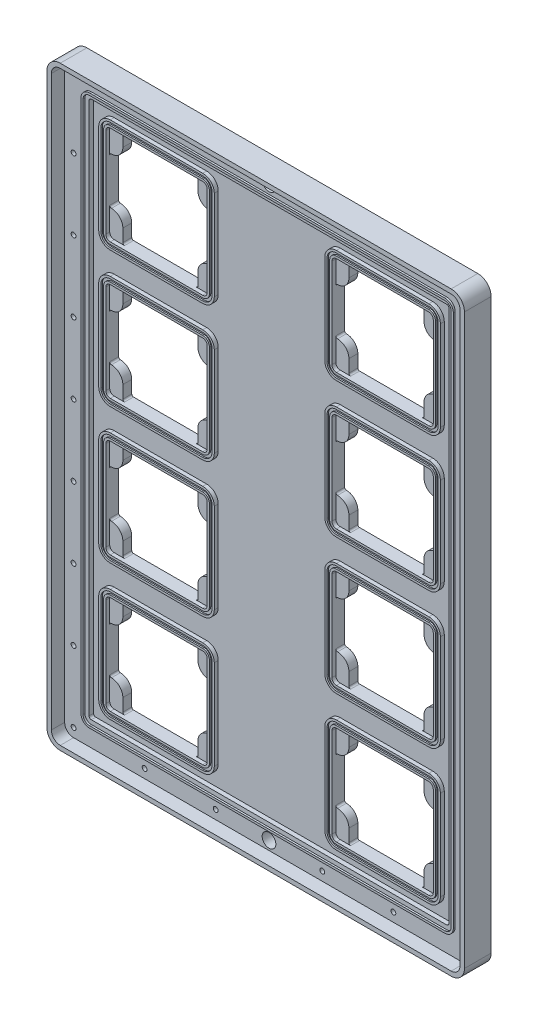
SolidWorks part; units mm, degrees
ref_plane "Front Plane" through (0, 0, 0) normal (0, 0, 1) x (1, 0, 0)
ref_plane "Top Plane" through (0, 0, 0) normal (0, 1, 0) x (1, 0, 0)
ref_plane "Right Plane" through (0, 0, 0) normal (1, 0, 0) x (0, 0, -1)
sketch "Sketch1" plane through (0, 0, 0) normal (0, 0, 1) x (1, 0, 0)
  line L1 (0, 0) -> (292.1, 0)
  line L2 (0, 0) -> (0, 419.1)
  line L3 (0, 419.1) -> (292.1, 419.1)
  line L4 (292.1, 0) -> (292.1, 419.1)
  dimension "D1" = 419.1
  dimension "D2" = 292.1
extrude "Boss-Extrude1" add sketch "Sketch1" along normal blind 9.525
sketch "Sketch4" plane through (0, 0, 9.525) normal (0, 0, 1) x (1, 0, 0)
  line L3 (0, 419.1) -> (0, 0) construction
  line L4 (6.35, 412.75) -> (285.75, 412.75) construction
  line L5 (6.35, 412.75) -> (6.35, 6.35) construction
  line L6 (6.35, 6.35) -> (285.75, 6.35) construction
  line L7 (285.75, 412.75) -> (285.75, 6.35) construction
  line L8 (292.1, 419.1) -> (0, 419.1) construction
  line L9 (292.1, 0) -> (292.1, 419.1) construction
  line L10 (0, 0) -> (292.1, 0) construction
  circle A0 centre (6.35, 6.35) radius 1.7272
  circle A1 centre (6.35, 412.75) radius 1.7272
  circle A2 centre (285.75, 412.75) radius 1.7272
  circle A3 centre (285.75, 6.35) radius 1.7272
  dimension "D5" = 3.4544
  dimension "D1" = 6.35
  dimension "D2" = 6.35
  dimension "D3" = 6.35
  dimension "D4" = 6.35
extrude "Cut-Extrude1" cut sketch "Sketch4" against normal blind 6.985
pattern_linear "LPattern2" count 8 spacing 50.8 along (0, -1, 0) of "Cut-Extrude1"
sketch "Sketch5" plane through (0, 0, 9.525) normal (0, 0, 1) x (1, 0, 0)
  line L0 (0, 419.1) -> (0, 0) construction
  line L1 (19.05, 406.4) -> (273.05, 406.4) construction
  line L2 (12.7, 400.05) -> (12.7, 19.05) construction
  line L3 (19.05, 12.7) -> (273.05, 12.7) construction
  line L4 (279.4, 400.05) -> (279.4, 19.05) construction
  line L5 (292.1, 419.1) -> (0, 419.1) construction
  line L6 (292.1, 0) -> (292.1, 419.1) construction
  line L7 (0, 0) -> (292.1, 0) construction
  line L8 (19.05, 14.732) -> (273.05, 14.732) construction
  line L9 (14.732, 400.05) -> (14.732, 19.05) construction
  line L10 (19.05, 404.368) -> (273.05, 404.368) construction
  line L11 (277.368, 400.05) -> (277.368, 19.05) construction
  line L12 (12.954, 400.05) -> (12.954, 19.05)
  line L13 (19.05, 406.146) -> (273.05, 406.146)
  line L14 (279.146, 400.05) -> (279.146, 19.05)
  line L15 (19.05, 12.954) -> (273.05, 12.954)
  line L16 (277.622, 400.05) -> (277.622, 19.05)
  line L17 (19.05, 404.622) -> (273.05, 404.622)
  line L18 (14.478, 400.05) -> (14.478, 19.05)
  line L19 (19.05, 14.478) -> (273.05, 14.478)
  arc A0 (273.05, 12.7) -> (279.4, 19.05) centre (273.05, 19.05) ccw construction
  arc A1 (12.7, 19.05) -> (19.05, 12.7) centre (19.05, 19.05) ccw construction
  arc A2 (273.05, 406.4) -> (279.4, 400.05) centre (273.05, 400.05) cw construction
  arc A3 (19.05, 406.4) -> (12.7, 400.05) centre (19.05, 400.05) ccw construction
  arc A4 (14.732, 19.05) -> (19.05, 14.732) centre (19.05, 19.05) ccw construction
  arc A5 (19.05, 404.368) -> (14.732, 400.05) centre (19.05, 400.05) ccw construction
  arc A6 (273.05, 404.368) -> (277.368, 400.05) centre (273.05, 400.05) cw construction
  arc A7 (273.05, 14.732) -> (277.368, 19.05) centre (273.05, 19.05) ccw construction
  arc A8 (19.05, 406.146) -> (12.954, 400.05) centre (19.05, 400.05) ccw
  arc A9 (273.05, 406.146) -> (279.146, 400.05) centre (273.05, 400.05) cw
  arc A10 (273.05, 12.954) -> (279.146, 19.05) centre (273.05, 19.05) ccw
  arc A11 (12.954, 19.05) -> (19.05, 12.954) centre (19.05, 19.05) ccw
  arc A12 (273.05, 404.622) -> (277.622, 400.05) centre (273.05, 400.05) cw
  arc A13 (19.05, 404.622) -> (14.478, 400.05) centre (19.05, 400.05) ccw
  arc A14 (14.478, 19.05) -> (19.05, 14.478) centre (19.05, 19.05) ccw
  arc A15 (273.05, 14.478) -> (277.622, 19.05) centre (273.05, 19.05) ccw
  dimension "D5" = 6.35
  dimension "D1" = 12.7
  dimension "D2" = 12.7
  dimension "D3" = 12.7
  dimension "D4" = 12.7
  dimension "D6" = 2.032
  dimension "D7" = 2.032
  dimension "D8" = 0.254
  dimension "D9" = 0.254
  dimension "D10" = 0.254
sketch "Sketch6" plane through (0, 0, 9.525) normal (0, 0, 1) x (1, 0, 0)
  line L0 (292.1, 419.1) -> (0, 419.1) construction
  line L1 (0, 419.1) -> (0, 0) construction
  line L24 (273.05, 401.6375) -> (19.05, 401.6375)
  line L25 (274.6375, 19.05) -> (274.6375, 400.05)
  line L26 (19.05, 17.4625) -> (273.05, 17.4625)
  line L27 (17.4625, 400.05) -> (17.4625, 19.05)
  line L28 (273.05, 401.6375) -> (19.05, 401.6375)
  line L29 (274.6375, 19.05) -> (274.6375, 400.05)
  line L30 (19.05, 17.4625) -> (273.05, 17.4625)
  line L31 (17.4625, 400.05) -> (17.4625, 19.05)
  arc A20 (19.05, 401.6375) -> (17.4625, 400.05) centre (19.05, 400.05) ccw
  arc A21 (274.6375, 400.05) -> (273.05, 401.6375) centre (273.05, 400.05) ccw
  arc A22 (273.05, 17.4625) -> (274.6375, 19.05) centre (273.05, 19.05) ccw
  arc A23 (17.4625, 19.05) -> (19.05, 17.4625) centre (19.05, 19.05) ccw
  arc A24 (19.05, 401.6375) -> (17.4625, 400.05) centre (19.05, 400.05) ccw
  arc A25 (274.6375, 400.05) -> (273.05, 401.6375) centre (273.05, 400.05) ccw
  arc A26 (273.05, 17.4625) -> (274.6375, 19.05) centre (273.05, 19.05) ccw
  arc A27 (17.4625, 19.05) -> (19.05, 17.4625) centre (19.05, 19.05) ccw
  dimension "D2" = 17.4625
  dimension "D3" = 17.4625
  dimension "D1" = 2.7305
extrude "Cut-Extrude3" cut sketch "Sketch6" against normal blind 3.175
extrude "Boss-Extrude2" add sketch "Sketch5" along normal blind 1.3335 contours L12 A11 L15 A10 L14 A9 L13 A8 A15 L19 A14 L18 A13 L17 A12 L16 region at (15.0752, 404.0248, 9.525)
fillet "Fillet1" radius 6.35 4 edges at (0, 419.1, 4.7625) (292.1, 419.1, 4.7625) (0, 0, 4.7625) (292.1, 0, 4.7625)
sketch "Sketch8" plane through (0, 0, 0) normal (0, 0, -1) x (-1, 0, 0)
  line L0 (-264.668, 370.459) -> (-264.668, 339.2678)
  line L1 (-255.27, 329.8698) -> (-255.27, 320.8782)
  line L2 (-252.4506, 318.0588) -> (-201.2442, 318.0588)
  line L3 (-198.4248, 320.8782) -> (-198.4248, 329.8698)
  line L4 (-189.0268, 339.2678) -> (-189.0268, 370.459)
  line L5 (-198.4248, 379.857) -> (-198.4248, 388.8486)
  line L6 (-201.2442, 391.668) -> (-252.4506, 391.668)
  line L7 (-255.27, 388.8486) -> (-255.27, 379.857)
  line L8 (-261.8486, 391.668) -> (-261.8486, 318.0588) construction
  line L9 (-264.668, 388.8486) -> (-189.0268, 388.8486) construction
  line L10 (-264.668, 391.668) -> (-189.0268, 391.668) construction
  line L11 (-264.668, 391.668) -> (-264.668, 318.0588) construction
  line L12 (-264.668, 318.0588) -> (-189.0268, 318.0588) construction
  line L13 (-189.0268, 391.668) -> (-189.0268, 318.0588) construction
  line L14 (-264.668, 379.857) -> (-189.0268, 379.857) construction
  line L15 (-264.668, 370.459) -> (-189.0268, 370.459) construction
  line L16 (-264.668, 339.2678) -> (-189.0268, 339.2678) construction
  line L17 (-264.668, 329.8698) -> (-189.0268, 329.8698) construction
  line L18 (-264.668, 320.8782) -> (-189.0268, 320.8782) construction
  line L19 (-255.27, 318.0588) -> (-255.27, 391.668) construction
  line L20 (-252.4506, 391.668) -> (-252.4506, 318.0588) construction
  line L21 (-201.2442, 391.668) -> (-201.2442, 318.0588) construction
  line L22 (-198.4248, 391.668) -> (-198.4248, 318.0588) construction
  line L23 (-191.8462, 318.0588) -> (-191.8462, 391.668) construction
  line L24 (-189.0268, 373.2784) -> (-264.668, 373.2784) construction
  line L27 (-201.2442, 393.7) -> (-252.4506, 393.7)
  line L28 (-257.302, 388.8486) -> (-257.302, 379.857)
  line L29 (-266.7, 370.459) -> (-266.7, 339.2678)
  line L30 (-257.302, 329.8698) -> (-257.302, 320.8782)
  line L31 (-252.4506, 316.0268) -> (-201.2442, 316.0268)
  line L32 (-196.3928, 320.8782) -> (-196.3928, 329.8698)
  line L33 (-186.9948, 339.2678) -> (-186.9948, 370.459)
  line L34 (-196.3928, 379.857) -> (-196.3928, 388.8486)
  line L35 (-285.75, 419.1) -> (-6.35, 419.1) construction
  line L36 (-292.1, 6.35) -> (-292.1, 412.75) construction
  arc A0 (-261.8486, 373.2784) -> (-255.27, 379.857) centre (-261.8486, 379.857) ccw
  arc A1 (-261.8486, 373.2784) -> (-264.668, 370.459) centre (-261.8486, 370.459) ccw
  arc A2 (-264.668, 339.2678) -> (-261.8486, 336.4484) centre (-261.8486, 339.2678) ccw
  arc A3 (-255.27, 329.8698) -> (-261.8486, 336.4484) centre (-261.8486, 329.8698) ccw
  arc A4 (-255.27, 320.8782) -> (-252.4506, 318.0588) centre (-252.4506, 320.8782) ccw
  arc A5 (-201.2442, 318.0588) -> (-198.4248, 320.8782) centre (-201.2442, 320.8782) ccw
  arc A6 (-191.8462, 336.4484) -> (-198.4248, 329.8698) centre (-191.8462, 329.8698) ccw
  arc A7 (-191.8462, 336.4484) -> (-189.0268, 339.2678) centre (-191.8462, 339.2678) ccw
  arc A8 (-189.0268, 370.459) -> (-191.8462, 373.2784) centre (-191.8462, 370.459) ccw
  arc A9 (-198.4248, 379.857) -> (-191.8462, 373.2784) centre (-191.8462, 379.857) ccw
  arc A10 (-198.4248, 388.8486) -> (-201.2442, 391.668) centre (-201.2442, 388.8486) ccw
  arc A11 (-252.4506, 391.668) -> (-255.27, 388.8486) centre (-252.4506, 388.8486) ccw
  arc A12 (-252.4506, 393.7) -> (-257.302, 388.8486) centre (-252.4506, 388.8486) ccw
  arc A13 (-261.8486, 375.3104) -> (-257.302, 379.857) centre (-261.8486, 379.857) ccw
  arc A14 (-261.8486, 375.3104) -> (-266.7, 370.459) centre (-261.8486, 370.459) ccw
  arc A15 (-266.7, 339.2678) -> (-261.8486, 334.4164) centre (-261.8486, 339.2678) ccw
  arc A16 (-257.302, 329.8698) -> (-261.8486, 334.4164) centre (-261.8486, 329.8698) ccw
  arc A17 (-257.302, 320.8782) -> (-252.4506, 316.0268) centre (-252.4506, 320.8782) ccw
  arc A18 (-201.2442, 316.0268) -> (-196.3928, 320.8782) centre (-201.2442, 320.8782) ccw
  arc A19 (-191.8462, 334.4164) -> (-196.3928, 329.8698) centre (-191.8462, 329.8698) ccw
  arc A20 (-191.8462, 334.4164) -> (-186.9948, 339.2678) centre (-191.8462, 339.2678) ccw
  arc A21 (-186.9948, 370.459) -> (-191.8462, 375.3104) centre (-191.8462, 370.459) ccw
  arc A22 (-196.3928, 379.857) -> (-191.8462, 375.3104) centre (-191.8462, 379.857) ccw
  arc A23 (-196.3928, 388.8486) -> (-201.2442, 393.7) centre (-201.2442, 388.8486) ccw
  dimension "D4" = 11.811
  dimension "D5" = 21.209
  dimension "D6" = 52.4002
  dimension "D1" = 73.6092
  dimension "D2" = 75.6412
  dimension "D3" = 2.8194
  dimension "D7" = 61.7982
  dimension "D8" = 70.7898
  dimension "D9" = 2.8194
  dimension "D10" = 9.398
  dimension "D11" = 12.2174
  dimension "D12" = 63.4238
  dimension "D13" = 66.2432
  dimension "D14" = 72.8218
  dimension "D15" = 55.2196
  dimension "D16" = 25.4
  dimension "D17" = 25.4
  dimension "D18" = 2.032
extrude "Cut-Extrude5" cut sketch "Sketch8" against normal blind 3.175
sketch "Sketch10" plane through (0, 0, 0) normal (0, 0, -1) x (-1, 0, 0)
  line L18 (-263.0805, 370.459) -> (-263.0805, 339.2678)
  line L19 (-253.6825, 329.8698) -> (-253.6825, 320.8782)
  line L20 (-252.4506, 319.6463) -> (-201.2442, 319.6463)
  line L21 (-200.0123, 320.8782) -> (-200.0123, 329.8698)
  line L22 (-190.6143, 339.2678) -> (-190.6143, 370.459)
  line L23 (-200.0123, 379.857) -> (-200.0123, 388.8486)
  line L24 (-201.2442, 390.0805) -> (-252.4506, 390.0805)
  line L25 (-253.6825, 388.8486) -> (-253.6825, 379.857)
  line L26 (-263.0805, 370.459) -> (-263.0805, 339.2678)
  line L27 (-253.6825, 329.8698) -> (-253.6825, 320.8782)
  line L28 (-252.4506, 319.6463) -> (-201.2442, 319.6463)
  line L29 (-200.0123, 320.8782) -> (-200.0123, 329.8698)
  line L30 (-190.6143, 339.2678) -> (-190.6143, 370.459)
  line L31 (-200.0123, 379.857) -> (-200.0123, 388.8486)
  line L32 (-201.2442, 390.0805) -> (-252.4506, 390.0805)
  line L33 (-253.6825, 388.8486) -> (-253.6825, 379.857)
  arc A28 (-261.8486, 371.6909) -> (-263.0805, 370.459) centre (-261.8486, 370.459) ccw
  arc A29 (-263.0805, 339.2678) -> (-261.8486, 338.0359) centre (-261.8486, 339.2678) ccw
  arc A30 (-253.6825, 329.8698) -> (-261.8486, 338.0359) centre (-261.8486, 329.8698) ccw
  arc A31 (-253.6825, 320.8782) -> (-252.4506, 319.6463) centre (-252.4506, 320.8782) ccw
  arc A32 (-201.2442, 319.6463) -> (-200.0123, 320.8782) centre (-201.2442, 320.8782) ccw
  arc A33 (-191.8462, 338.0359) -> (-200.0123, 329.8698) centre (-191.8462, 329.8698) ccw
  arc A34 (-191.8462, 338.0359) -> (-190.6143, 339.2678) centre (-191.8462, 339.2678) ccw
  arc A35 (-190.6143, 370.459) -> (-191.8462, 371.6909) centre (-191.8462, 370.459) ccw
  arc A36 (-200.0123, 379.857) -> (-191.8462, 371.6909) centre (-191.8462, 379.857) ccw
  arc A37 (-200.0123, 388.8486) -> (-201.2442, 390.0805) centre (-201.2442, 388.8486) ccw
  arc A38 (-252.4506, 390.0805) -> (-253.6825, 388.8486) centre (-252.4506, 388.8486) ccw
  arc A39 (-261.8486, 371.6909) -> (-253.6825, 379.857) centre (-261.8486, 379.857) ccw
  arc A40 (-261.8486, 371.6909) -> (-263.0805, 370.459) centre (-261.8486, 370.459) ccw
  arc A41 (-263.0805, 339.2678) -> (-261.8486, 338.0359) centre (-261.8486, 339.2678) ccw
  arc A42 (-253.6825, 329.8698) -> (-261.8486, 338.0359) centre (-261.8486, 329.8698) ccw
  arc A43 (-253.6825, 320.8782) -> (-252.4506, 319.6463) centre (-252.4506, 320.8782) ccw
  arc A44 (-201.2442, 319.6463) -> (-200.0123, 320.8782) centre (-201.2442, 320.8782) ccw
  arc A45 (-191.8462, 338.0359) -> (-200.0123, 329.8698) centre (-191.8462, 329.8698) ccw
  arc A46 (-191.8462, 338.0359) -> (-190.6143, 339.2678) centre (-191.8462, 339.2678) ccw
  arc A47 (-190.6143, 370.459) -> (-191.8462, 371.6909) centre (-191.8462, 370.459) ccw
  arc A48 (-200.0123, 379.857) -> (-191.8462, 371.6909) centre (-191.8462, 379.857) ccw
  arc A49 (-200.0123, 388.8486) -> (-201.2442, 390.0805) centre (-201.2442, 388.8486) ccw
  arc A50 (-252.4506, 390.0805) -> (-253.6825, 388.8486) centre (-252.4506, 388.8486) ccw
  arc A51 (-261.8486, 371.6909) -> (-253.6825, 379.857) centre (-261.8486, 379.857) ccw
  dimension "D1" = 1.5875
extrude "Cut-Extrude6" cut sketch "Sketch10" against normal through all
sketch "Sketch11" plane through (0, 0, 0) normal (0, 0, -1) x (-1, 0, 0)
  line L0 (-226.8474, 388.8994) -> (-226.8474, 393.7) construction
  line L1 (-261.8486, 388.8994) -> (-191.8462, 388.8994) construction
  line L2 (-261.8486, 388.8994) -> (-261.8486, 320.8274) construction
  line L3 (-261.8486, 320.8274) -> (-191.8462, 320.8274) construction
  line L4 (-191.8462, 388.8994) -> (-191.8462, 320.8274) construction
  line L5 (-201.2442, 393.7) -> (-252.4506, 393.7) construction
  line L6 (-226.8474, 320.8274) -> (-226.8474, 316.0268) construction
  line L7 (-252.4506, 316.0268) -> (-201.2442, 316.0268) construction
  line L8 (-261.8486, 354.8634) -> (-266.7, 354.8634) construction
  line L9 (-266.7, 370.459) -> (-266.7, 339.2678) construction
  line L10 (-191.8462, 354.8634) -> (-186.9948, 354.8634) construction
  line L11 (-186.9948, 339.2678) -> (-186.9948, 370.459) construction
  circle A0 centre (-261.8486, 388.8994) radius 1.1303
  circle A1 centre (-191.8462, 388.8994) radius 1.1303
  circle A2 centre (-191.8462, 320.8274) radius 1.1303
  circle A3 centre (-261.8486, 320.8274) radius 1.1303
  dimension "D3" = 2.2606
  dimension "D1" = 70.0024
  dimension "D2" = 68.072
extrude "Cut-Extrude7" cut sketch "Sketch11" against normal blind 3.9688
sketch "Sketch12" plane through (0, 0, 6.35) normal (0, 0, 1) x (1, 0, 0)
  line L0 (252.4506, 390.0805) -> (201.2442, 390.0805) construction
  line L1 (193.7893, 390.0805) -> (259.9055, 390.0805)
  line L2 (190.6143, 386.9055) -> (190.6143, 322.8213)
  line L3 (193.7893, 319.6463) -> (259.9055, 319.6463)
  line L4 (263.0805, 386.9055) -> (263.0805, 322.8213)
  line L5 (263.0805, 339.2678) -> (263.0805, 370.459) construction
  line L10 (193.7893, 391.668) -> (259.9055, 391.668)
  line L11 (264.668, 386.9055) -> (264.668, 322.8213)
  line L12 (193.7893, 318.0588) -> (259.9055, 318.0588)
  line L13 (189.0268, 386.9055) -> (189.0268, 322.8213)
  line L14 (187.1218, 386.9055) -> (187.1218, 322.8213)
  line L15 (193.7893, 316.1538) -> (259.9055, 316.1538)
  line L16 (266.573, 386.9055) -> (266.573, 322.8213)
  line L17 (193.7893, 393.573) -> (259.9055, 393.573)
  line L18 (185.5343, 386.9055) -> (185.5343, 322.8213)
  line L19 (193.7893, 314.5663) -> (259.9055, 314.5663)
  line L20 (268.1605, 386.9055) -> (268.1605, 322.8213)
  line L21 (193.7893, 395.1605) -> (259.9055, 395.1605)
  line L22 (201.2442, 319.6463) -> (252.4506, 319.6463) construction
  line L23 (190.6143, 370.459) -> (190.6143, 339.2678) construction
  arc A0 (259.9055, 319.6463) -> (263.0805, 322.8213) centre (259.9055, 322.8213) ccw
  arc A1 (190.6143, 322.8213) -> (193.7893, 319.6463) centre (193.7893, 322.8213) ccw
  arc A2 (259.9055, 390.0805) -> (263.0805, 386.9055) centre (259.9055, 386.9055) cw
  arc A3 (193.7893, 390.0805) -> (190.6143, 386.9055) centre (193.7893, 386.9055) ccw
  arc A4 (259.9055, 391.668) -> (264.668, 386.9055) centre (259.9055, 386.9055) cw
  arc A5 (259.9055, 318.0588) -> (264.668, 322.8213) centre (259.9055, 322.8213) ccw
  arc A6 (189.0268, 322.8213) -> (193.7893, 318.0588) centre (193.7893, 322.8213) ccw
  arc A7 (193.7893, 391.668) -> (189.0268, 386.9055) centre (193.7893, 386.9055) ccw
  arc A8 (187.1218, 322.8213) -> (193.7893, 316.1538) centre (193.7893, 322.8213) ccw
  arc A9 (259.9055, 316.1538) -> (266.573, 322.8213) centre (259.9055, 322.8213) ccw
  arc A10 (259.9055, 393.573) -> (266.573, 386.9055) centre (259.9055, 386.9055) cw
  arc A11 (193.7893, 393.573) -> (187.1218, 386.9055) centre (193.7893, 386.9055) ccw
  arc A12 (185.5343, 322.8213) -> (193.7893, 314.5663) centre (193.7893, 322.8213) ccw
  arc A13 (259.9055, 314.5663) -> (268.1605, 322.8213) centre (259.9055, 322.8213) ccw
  arc A14 (259.9055, 395.1605) -> (268.1605, 386.9055) centre (259.9055, 386.9055) cw
  arc A15 (193.7893, 395.1605) -> (185.5343, 386.9055) centre (193.7893, 386.9055) ccw
  dimension "D1" = 3.175
  dimension "D2" = 1.5875
  dimension "D3" = 1.905
  dimension "D4" = 1.5875
extrude "Boss-Extrude3" add sketch "Sketch12" along normal blind 2.794 contours L21 A15 L18 A12 L19 A13 L20 A14 A11 L17 A10 L16 A9 L15 A8 L14 | L10 A7 L13 A6 L12 A5 L11 A4 A3 L1 A2 L4 A0 L3 A1 L2 region at (226.8474, 390.6125, 6.35) region at (188.7683, 391.9265, 6.35)
extrude "Boss-Extrude4" add sketch "Sketch12<3>" along normal blind 1.778 contours L17 A11 L14 A8 L15 A9 L16 A10 A7 L10 A4 L11 A5 L12 A6 L13 region at (189.8591, 390.8357, 6.35)
sketch "Sketch12<3>" plane through (0, 0, 6.35) normal (0, 0, 1) x (1, 0, 0) same geometry as "Sketch12"
pattern_linear "LPattern1" count 2 spacing 161.5948 along (-1, 0, 0) count 4 spacing 96.8756 along (0, -1, 0) of "Cut-Extrude6", "Cut-Extrude5", "Cut-Extrude7", "Boss-Extrude3", "Boss-Extrude4"
sketch "Sketch13" plane through (0, 0, 0) normal (0, 0, -1) x (-1, 0, 0)
  line L4 (-6.35, 419.1) -> (-285.75, 419.1)
  line L5 (-292.1, 412.75) -> (-292.1, 6.35)
  line L6 (-285.75, 0) -> (-6.35, 0)
  line L7 (0, 6.35) -> (0, 412.75)
  line L8 (-285.75, -3.175) -> (-6.35, -3.175)
  line L9 (3.175, 6.35) -> (3.175, 412.75)
  line L10 (-6.35, 422.275) -> (-285.75, 422.275)
  line L11 (-295.275, 412.75) -> (-295.275, 6.35)
  line L12 (-285.75, -3.175) -> (-6.35, -3.175)
  line L13 (3.175, 6.35) -> (3.175, 412.75)
  line L14 (-6.35, 422.275) -> (-285.75, 422.275)
  line L15 (-295.275, 412.75) -> (-295.275, 6.35)
  arc A4 (-285.75, 419.1) -> (-292.1, 412.75) centre (-285.75, 412.75) ccw
  arc A5 (-292.1, 6.35) -> (-285.75, 0) centre (-285.75, 6.35) ccw
  arc A6 (-6.35, 0) -> (0, 6.35) centre (-6.35, 6.35) ccw
  arc A7 (0, 412.75) -> (-6.35, 419.1) centre (-6.35, 412.75) ccw
  arc A8 (-295.275, 6.35) -> (-285.75, -3.175) centre (-285.75, 6.35) ccw
  arc A9 (-6.35, -3.175) -> (3.175, 6.35) centre (-6.35, 6.35) ccw
  arc A10 (3.175, 412.75) -> (-6.35, 422.275) centre (-6.35, 412.75) ccw
  arc A11 (-285.75, 422.275) -> (-295.275, 412.75) centre (-285.75, 412.75) ccw
  arc A12 (-295.275, 6.35) -> (-285.75, -3.175) centre (-285.75, 6.35) ccw
  arc A13 (-6.35, -3.175) -> (3.175, 6.35) centre (-6.35, 6.35) ccw
  arc A14 (3.175, 412.75) -> (-6.35, 422.275) centre (-6.35, 412.75) ccw
  arc A15 (-285.75, 422.275) -> (-295.275, 412.75) centre (-285.75, 412.75) ccw
  dimension "D1" = 3.175
  dimension "D2" = 3.175
extrude "Boss-Extrude5" add sketch "Sketch13" against normal blind 19.05
sketch "Sketch14" plane through (0, 0, 9.525) normal (0, 0, 1) x (1, 0, 0)
  line L0 (285.75, 6.35) -> (6.35, 6.35) construction
  circle A0 centre (234.95, 6.35) radius 1.7272
  circle A1 centre (184.15, 6.35) radius 1.7272
  circle A2 centre (107.95, 6.35) radius 1.7272
  circle A3 centre (57.15, 6.35) radius 1.7272
  circle A4 centre (6.35, 6.35) radius 1.7272 construction
  dimension "D1" = 50.8
  dimension "D2" = 50.8
  dimension "D3" = 50.8
  dimension "D4" = 50.8
extrude "Cut-Extrude8" cut sketch "Sketch14" against normal blind 6.985
sketch "Sketch15" plane through (0, 0, 9.525) normal (0, 0, 1) x (1, 0, 0)
  line L0 (285.75, 6.35) -> (6.35, 6.35) construction
  circle A0 centre (146.05, 6.35) radius 4.9022
  dimension "D1" = 9.8044
extrude "Cut-Extrude9" cut sketch "Sketch15" against normal through all
pattern_linear "LPattern3" count 2 spacing 406.4 along (0, 1, 0) of "Cut-Extrude8", "Cut-Extrude9"
